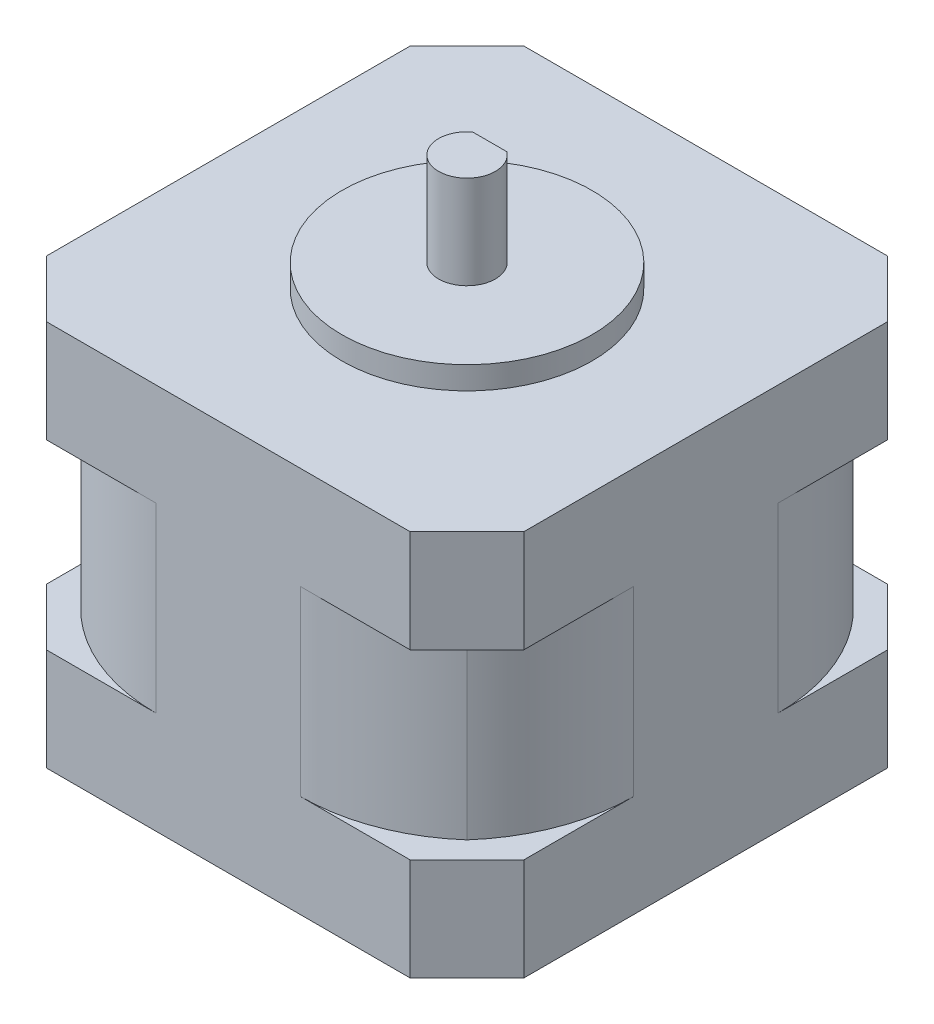
SolidWorks part; units mm, degrees
ref_plane "정면" through (0, 0, 0) normal (0, 0, 1) x (1, 0, 0)
ref_plane "윗면" through (0, 0, 0) normal (0, 1, 0) x (1, 0, 0)
ref_plane "우측면" through (0, 0, 0) normal (1, 0, 0) x (0, 0, -1)
sketch "스케치1" plane through (0, 0, 0) normal (0, 1, 0) x (1, 0, 0)
  line L1 (-21, -21) -> (21, -21)
  line L2 (-21, -21) -> (-21, 21)
  line L3 (-21, 21) -> (21, 21)
  line L4 (21, -21) -> (21, 21)
  line L5 (-21, -21) -> (21, 21) construction
  line L6 (-21, 21) -> (21, -21) construction
  point P0 (0, 0)
  dimension "D1" = 42
  dimension "D2" = 42
extrude "보스-돌출1" add sketch "스케치1" along normal mid plane 34
sketch "스케치2" plane through (0, 0, 0) normal (0, 1, 0) x (1, 0, 0)
  line L0 (-21, 13) -> (-13, 21)
  line L1 (-21, 21) -> (-21, -21) construction
  line L2 (21, 21) -> (-21, 21) construction
  line L3 (-13, 21) -> (-21, 21)
  line L4 (-21, 21) -> (-21, 13)
  dimension "D1" = 8
extrude "컷-돌출1" cut sketch "스케치2" against normal mid plane 16
pattern_circular "원형 패턴1" count 4 over 360 about axis through (0, 17, 0) along (0, 1, 0) of "컷-돌출1"
fillet "필렛1" radius 16 8 edges at (21, 0, -13) (13, 0, -21) (-13, 0, -21) (-21, 0, -13) (-21, 0, 13) (-13, 0, 21) (13, 0, 21) (21, 0, 13)
chamfer "모따기1" distance 5 angle 45 8 edges at (21, -12.5, -21) (21, -12.5, 21) (-21, -12.5, -21) (-21, -12.5, 21) (-21, 12.5, 21) (21, 12.5, 21) (21, 12.5, -21) (-21, 12.5, -21)
sketch "스케치3" plane through (0, 17, 0) normal (0, 1, 0) x (1, 0, 0)
  circle A0 centre (0, 0) radius 11
  dimension "D1" = 22
extrude "보스-돌출2" add sketch "스케치3" along normal blind 2
sketch "스케치4" plane through (0, 19, 0) normal (0, 1, 0) x (1, 0, 0)
  line L0 (-1.5, 2) -> (1.5, 2)
  line L1 (0, 2) -> (0, -2.5) construction
  circle A0 centre (0, 0) radius 2.5
  dimension "D1" = 5
  dimension "D2" = 4.5
extrude "보스-돌출3" add sketch "스케치4" along normal blind 8.2 contours L1 L0 A0 | L0 L1 A0 region at (-1.0879, 19, 0.1209) region at (1.0879, 19, 0.1209)
